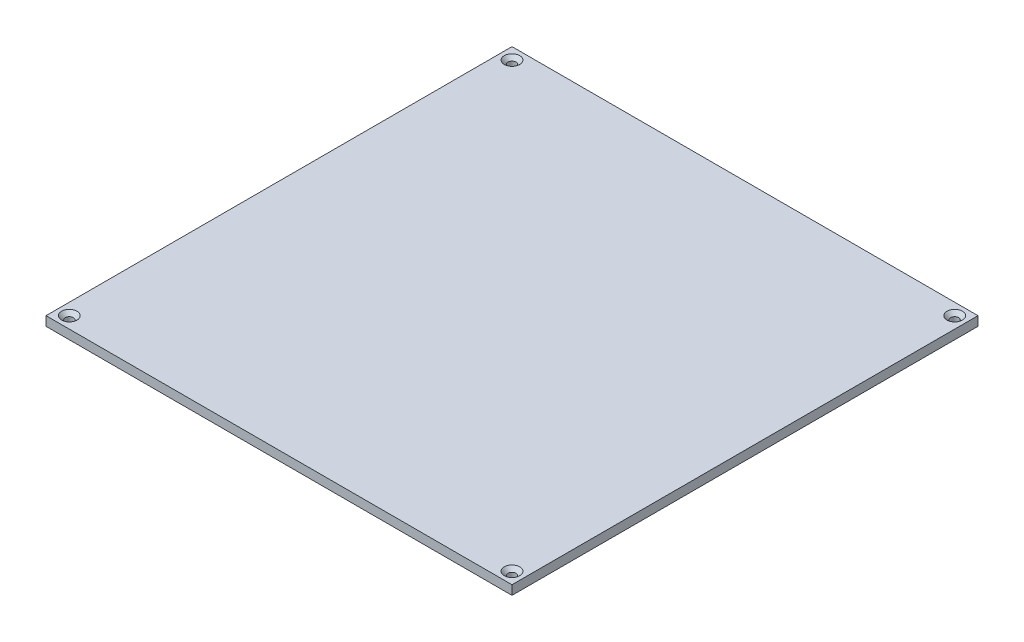
SolidWorks part; units mm, degrees
material "6061-T6 (SS)"
ref_plane "Front Plane" through (0, 0, 0) normal (0, 0, 1) x (1, 0, 0)
ref_plane "Top Plane" through (0, 0, 0) normal (0, 1, 0) x (1, 0, 0)
ref_plane "Right Plane" through (0, 0, 0) normal (1, 0, 0) x (0, 0, -1)
sketch "Sketch1" plane through (0, 0, 0) normal (0, 1, 0) x (1, 0, 0)
  line L0 (160, -160) -> (160, 160)
  line L1 (160, 160) -> (-160, 160)
  line L2 (-160, 160) -> (-160, -160)
  line L3 (-160, -160) -> (160, -160)
  line L4 (0, 160) -> (0, -160) construction
  line L5 (-160, 0) -> (160, 0) construction
  circle A0 centre (152, 152) radius 2.525
  circle A1 centre (-152, -152) radius 2.525
  circle A2 centre (152, -152) radius 2.525
  circle A3 centre (-152, 152) radius 2.525
  point P16 (-152, 154.525)
  point P17 (-154.525, 152)
  dimension "D2" = 304
  dimension "D3" = 304
  dimension "D4" = 5.05
  dimension "D1" = 320
extrude "Boss-Extrude1" add sketch "Sketch1" against normal blind 6.35
chamfer "Chamfer1" [suppressed] distance 3 angle 50
sketch "Sketch2" plane through (0, -6.35, 0) normal (0, -1, 0) x (1, 0, 0)
  line L0 (-160, -120) -> (-160, -160)
  line L1 (-160, -113) -> (-160, -120) construction
  line L2 (-3.5, -160) -> (3.5, -160) construction
  line L3 (3.5, -160) -> (160, -160)
  line L4 (160, 160) -> (-160, 160)
  line L5 (-160, 160) -> (-160, -160)
  line L6 (-160, -160) -> (160, -160)
  line L7 (160, -160) -> (160, 160)
  line L8 (160, 160) -> (120, 160)
  line L9 (-160, 160) -> (-160, -113)
  line L10 (-160, -160) -> (-3.5, -160)
  line L11 (160, -160) -> (160, -120)
  line L12 (160, -120) -> (160, -113) construction
  line L13 (160, -113) -> (160, 160)
  line L14 (120, 160) -> (113, 160) construction
  line L15 (113, 160) -> (-113, 160)
  line L16 (-113, 160) -> (-120, 160) construction
  line L17 (-120, 160) -> (-160, 160)
  point P15 (0, -160)
  dimension "D2" = 7
  dimension "D3" = 40
  dimension "D4" = 40
  dimension "D5" = 40
  dimension "D6" = 40
  dimension "D1" = 0
hole_wizard "CSK for M5 Flat Head Machine Screw1" positions "3DSketch1" profile "Sketch3" countersink size "M5" standard "ANSI Metric" end condition up to next
sketch3d "3DSketch1"
  line L0 (-152, -6.35, -152) -> (-152, 0, -152) construction
  line L1 (152, -6.35, -152) -> (152, 0, -152) construction
  line L2 (152, -6.35, 152) -> (152, 0, 152) construction
  line L3 (-152, -6.35, 152) -> (-152, 0, 152) construction
  point P0 (-152, 0, -152)
  point P4 (152, 0, -152)
  point P8 (152, 0, 152)
  point P12 (-152, 0, 152)
sketch "Sketch3" plane through (-152, 0, -152) normal (1, 0, 0) x (0, 0, 1)
  line L0 (0, 0) -> (0, 6.35)
  line L1 (0, 6.35) -> (2.75, 6.35)
  line L2 (2.75, 6.35) -> (2.75, 2.55)
  line L3 (2.75, 2.55) -> (5.3, 0)
  line L5 (5.3, 0) -> (0, 0)
  line L6 (-2.75, 2.55) -> (-5.3, 0) construction
  line L11 (0, -6.35) -> (0, 107.95) construction
  dimension "Thru Hole Dia." = 5.5
  dimension "Thru Hole Depth" = 6.35
  dimension "Near C'Sink Dia." = 10.6
  dimension "Near C'Sink Angle" = 90
equation "\"D4@Sketch2\"=\"D3@Sketch2\""
equation "\"D6@Sketch2\"=\"D3@Sketch2\""
equation "\"D5@Sketch2\"=\"D3@Sketch2\""
